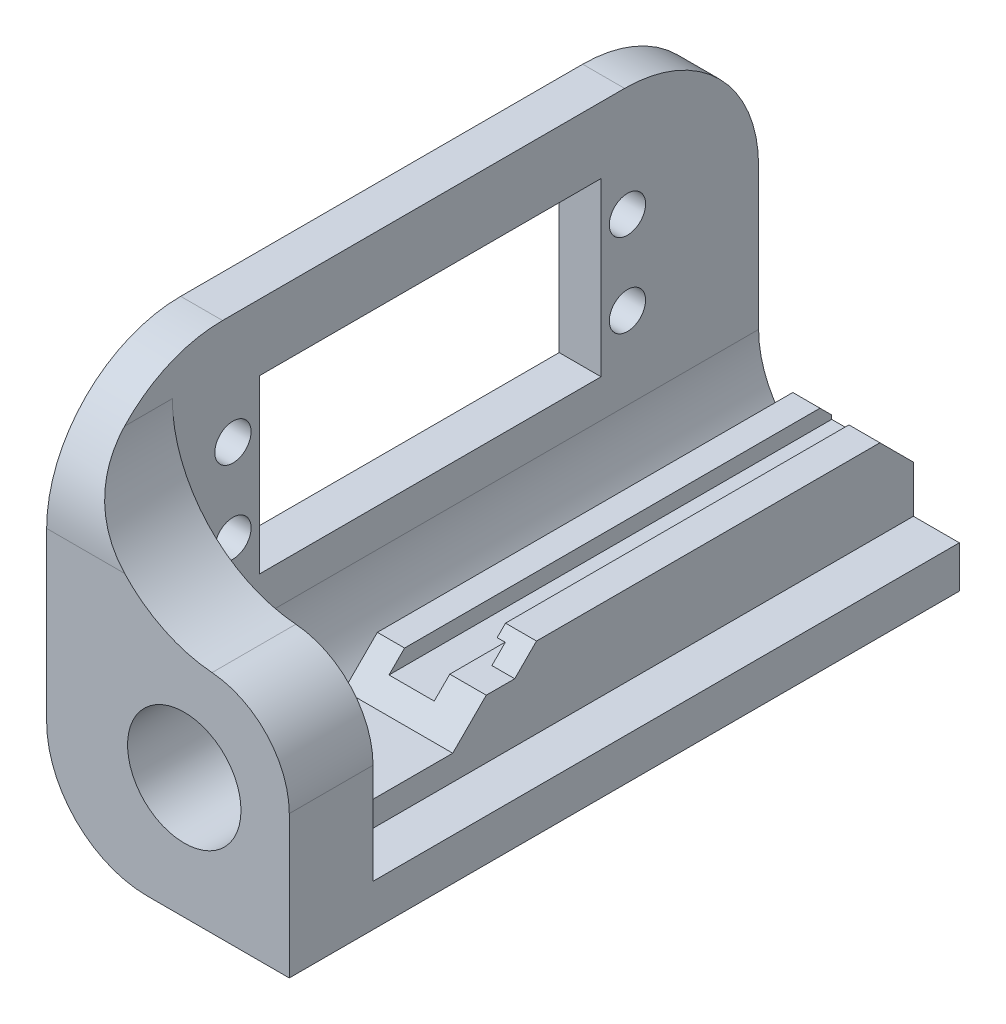
SolidWorks part; units mm, degrees
ref_plane "Alzado" through (0, 0, 0) normal (0, 0, 1) x (1, 0, 0)
ref_plane "Planta" through (0, 0, 0) normal (0, 1, 0) x (1, 0, 0)
ref_plane "Vista lateral" through (0, 0, 0) normal (1, 0, 0) x (0, 0, -1)
sketch "Croquis1" plane through (0, 0, 0) normal (0, 1, 0) x (1, 0, 0)
  line L1 (-45, 40) -> (45, 40)
  line L2 (-45, 40) -> (-45, -40)
  line L3 (-45, -40) -> (45, -40)
  line L4 (45, 40) -> (45, -40)
  line L5 (-45, 40) -> (45, -40) construction
  line L6 (-45, -40) -> (45, 40) construction
  point P0 (0, 0)
  dimension "D1" = 90
  dimension "D2" = 80
extrude "Saliente-Extruir1" add sketch "Croquis1" along normal blind 50
sketch "Croquis2" plane through (0, 50, 0) normal (0, 1, 0) x (1, 0, 0)
  line L0 (45, 40) -> (-45, 40) construction
  line L1 (-40, 40) -> (45, 40)
  line L2 (-40, 40) -> (-40, -40)
  line L3 (-40, -40) -> (45, -40)
  line L4 (45, 40) -> (45, -40)
  line L7 (-45, 40) -> (-45, -40) construction
  dimension "D1" = 5
extrude "Cortar-Extruir1" cut sketch "Croquis2" against normal blind 23
sketch "Croquis3" plane through (0, 27, 0) normal (0, 1, 0) x (1, 0, 0)
  line L0 (-40, -40) -> (45, -40) construction
  line L1 (45, 40) -> (-16.0328, 40)
  line L2 (45, 40) -> (45, -40)
  line L3 (45, -40) -> (-16.0328, -40)
  line L4 (-16.0328, 40) -> (-16.0328, -40)
extrude "Cortar-Extruir2" cut sketch "Croquis3" against normal blind 32
sketch "Croquis4" plane through (0, 27, 0) normal (0, 1, 0) x (1, 0, 0)
  line L0 (-16.0328, 40) -> (-16.0328, -40) construction
  line L1 (-40, 40) -> (-16.0328, 40)
  line L2 (-40, 40) -> (-40, -30)
  line L3 (-40, -30) -> (-16.0328, -30)
  line L4 (-16.0328, 40) -> (-16.0328, -30)
  dimension "D1" = 70
extrude "Cortar-Extruir3" cut sketch "Croquis4" against normal blind 22
sketch "Croquis7" plane through (0, 0, 40) normal (0, 0, 1) x (1, 0, 0)
  circle A0 centre (-28.5692, 14.4443) radius 6.77
  circle A1 centre (-28.5692, 14.4443) radius 6.67 construction
  dimension "D1" = 0.1
extrude "Cortar-Extruir6" cut sketch "Croquis7" against normal blind 10
sketch "Croquis11" plane through (0, 5, 0) normal (0, 1, 0) x (1, 0, 0)
  line L0 (-28.0164, 40) -> (-28.0164, -30) construction
  line L1 (-16.0328, 40) -> (-40, 40) construction
  line L2 (-40, -30) -> (-16.0328, -30) construction
  line L3 (-40, 5) -> (-16.0328, 5) construction
  line L4 (-40, 40) -> (-40, -30) construction
  line L5 (-16.0328, -30) -> (-16.0328, 40) construction
  line L7 (-34.5164, -30) -> (-21.5164, -30)
  line L8 (-34.5164, -30) -> (-34.5164, 40)
  line L9 (-34.5164, 40) -> (-21.5164, 40)
  line L10 (-21.5164, -30) -> (-21.5164, 40)
  line L11 (-34.5164, -30) -> (-21.5164, 40) construction
  line L12 (-34.5164, 40) -> (-21.5164, -30) construction
  point P12 (-28.0164, 5)
  dimension "D1" = 13
extrude "Saliente-Extruir2" add sketch "Croquis11" along normal blind 2
sketch "Croquis12" plane through (0, 7, 0) normal (0, 1, 0) x (1, 0, 0)
  line L0 (-21.5164, -30) -> (-21.5164, 40) construction
  line L1 (-34.5164, 40) -> (-21.5164, 40)
  line L2 (-34.5164, 40) -> (-34.5164, -15)
  line L3 (-34.5164, -15) -> (-21.5164, -15)
  line L4 (-21.5164, 40) -> (-21.5164, -15)
  dimension "D1" = 55
extrude "Saliente-Extruir3" add sketch "Croquis12" along normal blind 5
fillet "Redondeo3" radius 12 1 edges at (-40, 5, -5)
fillet "Redondeo4" radius 12 1 edges at (-45, 0, 0)
sketch "Croquis14" plane through (0, 7, 0) normal (0, 1, 0) x (1, 0, 0)
  line L0 (-21.5164, -30) -> (-21.5164, 40) construction
  line L1 (-34.5164, -15) -> (-21.5164, -15)
  line L2 (-34.5164, -15) -> (-34.5164, -28)
  line L3 (-34.5164, -28) -> (-21.5164, -28)
  line L4 (-21.5164, -15) -> (-21.5164, -28)
  dimension "D1" = 13
extrude "Saliente-Extruir4" add sketch "Croquis14" along normal blind 1
sketch "Croquis17" plane through (0, 12, 0) normal (0, 1, 0) x (1, 0, 0)
  line L0 (-24.2432, 40) -> (-24.2432, -10)
  line L1 (-21.5164, 40) -> (-34.5164, 40) construction
  line L2 (-24.2432, -10) -> (-21.5164, -10)
  line L3 (-21.5164, -15) -> (-21.5164, 40) construction
  line L4 (-21.5164, -10) -> (-21.5164, 40)
  line L5 (-21.5164, 40) -> (-24.2432, 40)
  line L6 (-34.5164, -15) -> (-21.5164, -15) construction
  dimension "D1" = 5
extrude "Saliente-Extruir5" add sketch "Croquis17" along normal blind 1.6
sketch "Croquis18" plane through (0, 13.6, 0) normal (0, 1, 0) x (1, 0, 0)
  line L15 (-24.2432, 40) -> (-34.5164, 40) construction
  line L16 (-21.5164, -10) -> (-26.5164, -10)
  line L17 (-21.5164, -10) -> (-21.5164, 40)
  line L18 (-21.5164, 40) -> (-26.5164, 40)
  line L19 (-26.5164, -10) -> (-26.5164, 40)
  dimension "D1" = 5
extrude "Saliente-Extruir6" add sketch "Croquis18" along normal blind 1
chamfer "Chaflán2" distance 4 angle 45 1 edges at (-28.0164, 12, 15)
chamfer "Chaflán4" distance 4 angle 45 1 edges at (-24.0164, 14.6, -40)
sketch "Croquis19" plane through (-45, 0, 0) normal (-1, 0, 0) x (0, 0, 1)
  line L0 (-24.3402, 34.8107) -> (-24.3402, 24.8607) construction
  line L1 (22.7598, 34.8107) -> (22.7598, 24.8607) construction
  line L2 (-24.3402, 29.8357) -> (22.7598, 29.8357) construction
  circle A0 centre (-24.3402, 34.8107) radius 2.165
  circle A1 centre (-24.3402, 24.8607) radius 2.165
  circle A2 centre (22.7598, 34.8107) radius 2.165
  circle A3 centre (22.7598, 24.8607) radius 2.165
extrude "Cortar-Extruir10" cut sketch "Croquis19" against normal blind 10
sketch "Croquis20" plane through (0, 0, -40) normal (0, 0, -1) x (-1, 0, 0)
  line L0 (25.8692, 12) -> (25.8692, 10.1422)
  line L1 (24.2432, 12) -> (34.5164, 12) construction
  line L2 (25.8692, 10.1422) -> (31.2692, 10.1422)
  line L3 (31.2692, 10.1422) -> (31.2692, 12)
  line L4 (31.2692, 12) -> (25.8692, 12)
  line L5 (26.0692, 10.3422) -> (26.0692, 12.0427) construction
  line L6 (31.0692, 10.3422) -> (26.0692, 10.3422) construction
  line L7 (31.0692, 12.0427) -> (31.0692, 10.3422) construction
  dimension "D1" = 0.2
  dimension "D2" = 0.2
  dimension "D3" = 0.2
extrude "Cortar-Extruir11" cut sketch "Croquis20" against normal blind 80
sketch "Croquis22" plane through (0, 5, 0) normal (0, 1, 0) x (1, 0, 0)
  line L0 (-16.0328, 40) -> (-21.5164, 40) construction
  line L1 (-16.0328, -30) -> (-20.3236, -30)
  line L2 (-16.0328, -30) -> (-16.0328, 40)
  line L3 (-16.0328, 40) -> (-20.3236, 40)
  line L4 (-20.3236, -30) -> (-20.3236, 40)
fillet "Redondeo10" radius 10 1 edges at (-16.0328, 27, 35)
sketch "Croquis23" plane through (-40, 0, 0) normal (1, 0, 0) x (0, 0, -1)
  line L0 (-19.3098, 39.7857) -> (-19.3098, 29.8357) construction
  line L1 (21.1902, 19.5857) -> (-19.6098, 19.5857)
  line L2 (21.1902, 19.5857) -> (21.1902, 40.0857)
  line L3 (21.1902, 40.0857) -> (-19.6098, 40.0857)
  line L4 (-19.6098, 19.5857) -> (-19.6098, 40.0857)
  line L5 (20.8902, 19.8857) -> (20.8902, 39.7857) construction
  line L6 (15.5202, 39.7857) -> (-9.3598, 39.7857) construction
  line L7 (15.5202, 19.8857) -> (20.8902, 19.8857) construction
  dimension "D1" = 0.3
  dimension "D2" = 0.3
  dimension "D3" = 0.3
  dimension "D4" = 0.3
extrude "Cortar-Extruir12" cut sketch "Croquis23" against normal blind 22
sketch "Croquis24" plane through (0, 50, 0) normal (0, 1, 0) x (1, 0, 0)
  line L1 (-45, 40) -> (-40, 40)
  line L2 (-45, 40) -> (-45, -40)
  line L3 (-45, -40) -> (-40, -40)
  line L4 (-40, 40) -> (-40, -40)
extrude "Cortar-Extruir14" cut sketch "Croquis24" against normal blind 2
fillet "Redondeo13" radius 16 2 edges at (-42.5, 48, 40) (-42.5, 48, -40)
fillet "Redondeo14" radius 16 1 edges at (-40, 27, 35)
sketch "Croquis25" plane through (-26.5164, 0, 0) normal (-1, 0, 0) x (0, 0, 1)
  line L2 (-36, 14.6) -> (10, 14.6)
  line L3 (10, 14.6) -> (10, 13.6)
  line L4 (10, 14.6) -> (10, 13.6) construction
  line L6 (-36, 14.6) -> (-37, 13.6)
  line L7 (-37, 13.6) -> (10, 13.6)
extrude "Cortar-Extruir16" cut sketch "Croquis25" against normal blind 1.3
chamfer "Chaflán5" distance 5 angle 45 1 edges at (-23.3664, 14.6, 10)
